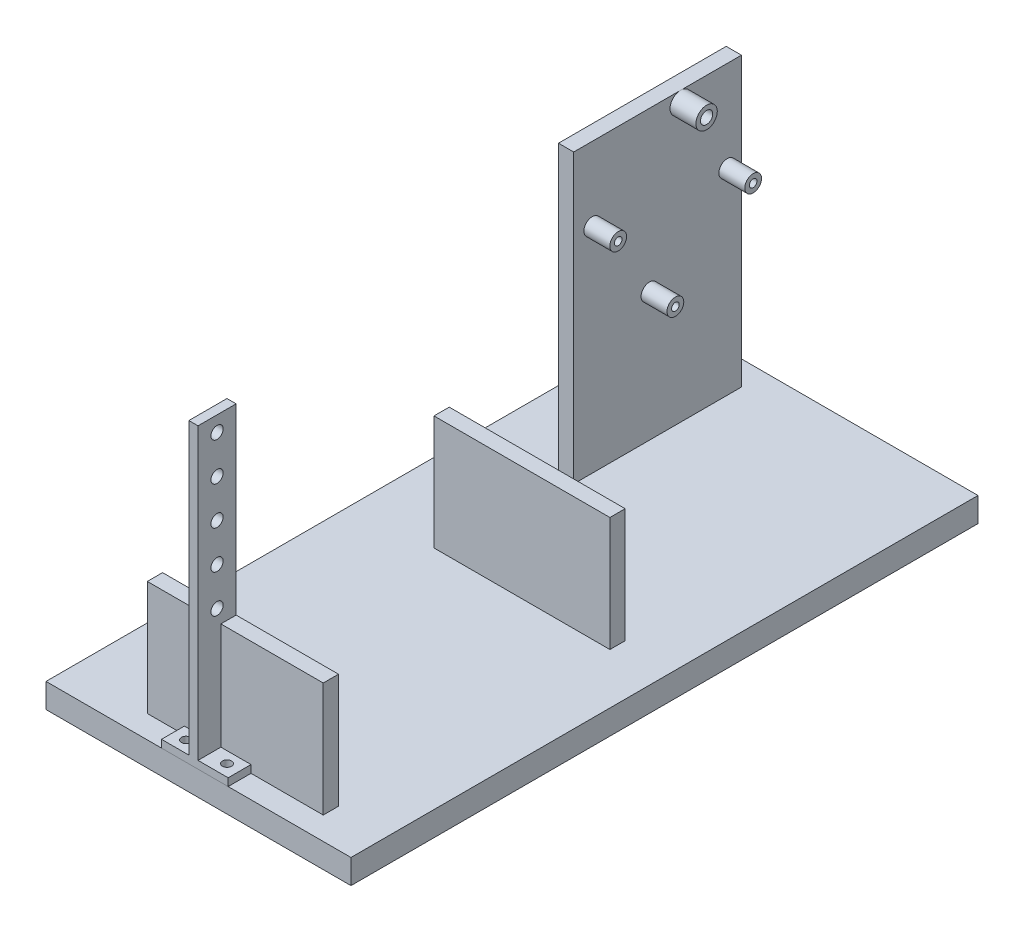
SolidWorks part; units mm, degrees
ref_plane "Front Plane" through (0, 0, 0) normal (0, 0, 1) x (1, 0, 0)
ref_plane "Top Plane" through (0, 0, 0) normal (0, 1, 0) x (1, 0, 0)
ref_plane "Right Plane" through (0, 0, 0) normal (1, 0, 0) x (0, 0, -1)
sketch "Sketch1" plane through (0, 0, 0) normal (0, 1, 0) x (1, 0, 0)
  line L1 (-100, 113) -> (100, 113)
  line L2 (-100, 113) -> (-100, -100)
  line L3 (-100, -100) -> (100, -100)
  line L4 (100, 113) -> (100, -100)
  point P0 (0, 0)
  dimension "D1" = 200
  dimension "D2" = 213
extrude "Boss-Extrude1" add sketch "Sketch1" against normal blind 16
sketch "Sketch2" plane through (0, 0, 0) normal (0, 1, 0) x (1, 0, 0)
  line L0 (-3.3156, -100) -> (-3.3156, 63.9577) construction
  line L1 (-100, -100) -> (100, -100) construction
  line L2 (-0.3156, -100) -> (-0.3156, -75)
  line L3 (-6.3156, -100) -> (-6.3156, -75)
  line L4 (-6.3156, -100) -> (-0.3156, -100)
  line L5 (-6.3156, -75) -> (-0.3156, -75)
  line L6 (-6.3156, -100) -> (-6.3156, 63.9577) construction
  line L7 (-0.3156, -100) -> (-0.3156, 63.9577) construction
  dimension "D1" = 3
  dimension "D3" = 25
  dimension "D2" = 3
extrude "Boss-Extrude2" add sketch "Sketch2" along normal blind 195 separate body
sketch "Sketch3" plane through (-0.3156, 0, 0) normal (1, 0, 0) x (0, 0, -1)
  line L0 (-87.5, 195) -> (-87.5, -2.6182) construction
  line L1 (-100, 195) -> (-75, 195) construction
  line L2 (-100, 0) -> (113, 0) construction
  circle A0 centre (-87.5, 160) radius 4
  circle A1 centre (-87.5, 135) radius 4
  circle A2 centre (-87.5, 110) radius 4
  circle A3 centre (-87.5, 85) radius 4
  circle A5 centre (-87.5, 185) radius 4
  circle A6 centre (-87.5, 60) radius 4 [skipped]
  dimension "D1" = 8
  dimension "D2" = 160
  dimension "D3" = 5
extrude "Cut-Extrude1" cut sketch "Sketch3" against normal blind 186.9
sketch "Sketch4" plane through (0, 0, 0) normal (0, 1, 0) x (1, 0, 0)
  line L1 (-48.5604, 113) -> (66.8081, 113)
  line L2 (-48.5604, 113) -> (-48.5604, 103)
  line L3 (-48.5604, 103) -> (66.8081, 103)
  line L4 (66.8081, 113) -> (66.8081, 103)
  dimension "D1" = 10
extrude "Boss-Extrude3" add sketch "Sketch4" along normal blind 75
sketch "Sketch5" plane through (0, 0, 75) normal (0, 0, -1) x (-1, 0, 0)
  line L4 (-66.8081, 0) -> (48.5604, 0)
  line L5 (-66.8081, 75) -> (-66.8081, 0)
  line L6 (48.5604, 75) -> (-66.8081, 75)
  line L7 (48.5604, 0) -> (48.5604, 75)
  line L8 (-66.8081, 0) -> (48.5604, 0)
  line L9 (-66.8081, 75) -> (-66.8081, 0)
  line L10 (48.5604, 75) -> (-66.8081, 75)
  line L11 (48.5604, 0) -> (48.5604, 75)
  dimension "D1" = 0
extrude "Boss-Extrude4" add sketch "Sketch5" against normal blind 10
sketch "Sketch6" plane through (0, 0, -113) normal (0, 0, -1) x (-1, 0, 0)
  line L1 (-100, -16) -> (100, -16)
  line L2 (-100, -16) -> (-100, 0)
  line L3 (-100, 0) -> (100, 0)
  line L4 (100, -16) -> (100, 0)
extrude "Boss-Extrude5" add sketch "Sketch6" along normal blind 198.2
sketch "Sketch7" plane through (0, 0, 0) normal (0, 1, 0) x (1, 0, 0)
  line L1 (-39.1321, 295.2) -> (-39.1321, 185.2)
  line L3 (-100, 311.2) -> (100, 311.2) construction
  line L4 (-49.1321, 295.2) -> (-49.1321, 185.2)
  line L5 (-39.1321, 295.2) -> (-49.1321, 295.2)
  line L6 (-39.1321, 185.2) -> (-49.1321, 185.2)
  dimension "D1" = 16
  dimension "D2" = 110
  dimension "D3" = 10
extrude "Boss-Extrude6" add sketch "Sketch7" along normal blind 188.5
sketch "Sketch8" plane through (-49.1321, 0, 0) normal (-1, 0, 0) x (0, 0, 1)
  circle A0 centre (-234.8847, 84.3047) radius 2.5 construction
  circle A1 centre (-285.8847, 128.9047) radius 2.5 construction
  circle A2 centre (-197.3847, 140.2047) radius 2.5 construction
  circle A3 centre (-255.3559, 181.523) radius 4 construction
  circle A4 centre (-234.8847, 84.3047) radius 2.5
  circle A5 centre (-285.8847, 128.9047) radius 2.5
  circle A6 centre (-197.3847, 140.2047) radius 2.5
  circle A7 centre (-255.3559, 181.523) radius 4
extrude "Cut-Extrude2" cut sketch "Sketch8" against normal up to surface (10 mm away) up to face at (-39.1321, 94.25, -240.2)
sketch "Sketch9" plane through (-39.1321, 0, 0) normal (1, 0, 0) x (0, 0, -1)
  circle A0 centre (255.3559, 181.523) radius 4 construction
  circle A1 centre (197.3847, 140.2047) radius 2.5 construction
  circle A2 centre (234.8847, 84.3047) radius 2.5 construction
  circle A3 centre (285.8847, 128.9047) radius 2.5 construction
  circle A4 centre (255.3559, 181.523) radius 4
  circle A5 centre (197.3847, 140.2047) radius 2.5
  circle A6 centre (234.8847, 84.3047) radius 2.5
  circle A7 centre (285.8847, 128.9047) radius 2.5
  circle A8 centre (255.3559, 181.523) radius 7
  circle A9 centre (197.3847, 140.2047) radius 5.5
  circle A10 centre (234.8847, 84.3047) radius 5.5
  circle A11 centre (285.8847, 128.9047) radius 5.5
  dimension "D1" = 3
extrude "Boss-Extrude7" add sketch "Sketch9" along normal blind 17
sketch "Sketch10" plane through (-49.1321, 0, 0) normal (-1, 0, 0) x (0, 0, 1)
  line L0 (-248.3788, 181.523) -> (-248.3788, 174.873)
  line L1 (-197.3847, 152.873) -> (-226.3788, 152.873)
  line L2 (-262.3329, 181.523) -> (-262.3329, 168.2201)
  line L3 (-285.8847, 138.2201) -> (-292.3329, 138.2201)
  line L4 (-295.2, 188.5) -> (-295.2, 0) construction
  line L5 (-295.2, 188.5) -> (-185.2, 188.5) construction
  line L6 (-185.2, 188.5) -> (-185.2, 0) construction
  line L7 (-295.2, 188.5) -> (-295.2, 0)
  line L8 (-295.2, 188.5) -> (-185.2, 188.5)
  line L9 (-185.2, 188.5) -> (-185.2, 143.6718)
  arc A0 (-248.3788, 181.523) -> (-262.3329, 181.523) centre (-255.3559, 181.523) ccw
  arc A1 (-285.8847, 138.2201) -> (-295.2, 128.9047) centre (-285.8847, 128.9047) ccw
  arc A2 (-185.2, 143.6718) -> (-197.3847, 152.873) centre (-197.3847, 140.2047) ccw
  arc A3 (-262.3329, 168.2201) -> (-292.3329, 138.2201) centre (-292.3329, 168.2201) cw
  arc A4 (-248.3788, 174.873) -> (-226.3788, 152.873) centre (-226.3788, 174.873) ccw
  line M6 (-185.2, 0) -> (-185.2, 188.5)
  line M7 (-185.2, 188.5) -> (-295.2, 188.5)
  line M8 (-295.2, 188.5) -> (-295.2, 0)
  dimension "D1" = 30
  dimension "D2" = 22
extrude "Cut-Extrude3" cut sketch "Sketch10" against normal blind 17 contours A3 L2 A0 L8 A1 L3 M8 | L0 A4 L1 A2 A0 M6 M7 rebuild error yes
sketch "Sketch12" plane through (0, 0, 0) normal (0, 1, 0) x (1, 0, 0)
  line L0 (-100, -100) -> (100, -100) construction
  line L1 (-24.252, -100) -> (19.4506, -100)
  line L2 (-24.252, -85) -> (19.4506, -85)
  line L3 (-24.252, -85) -> (-24.252, -100)
  line L4 (19.4506, -85) -> (19.4506, -100)
  line L5 (-100, -85) -> (100, -85) construction
  line L6 (-100, -100) -> (100, -100) construction
  line L8 (-2.4007, -100) -> (-2.4007, -110.8921) construction
  circle A0 centre (-15.8394, -92.3294) radius 3
  circle A1 centre (11.038, -92.3294) radius 3
  dimension "D1" = 15
extrude "Boss-Extrude9" add sketch "Sketch12" along normal blind 5
